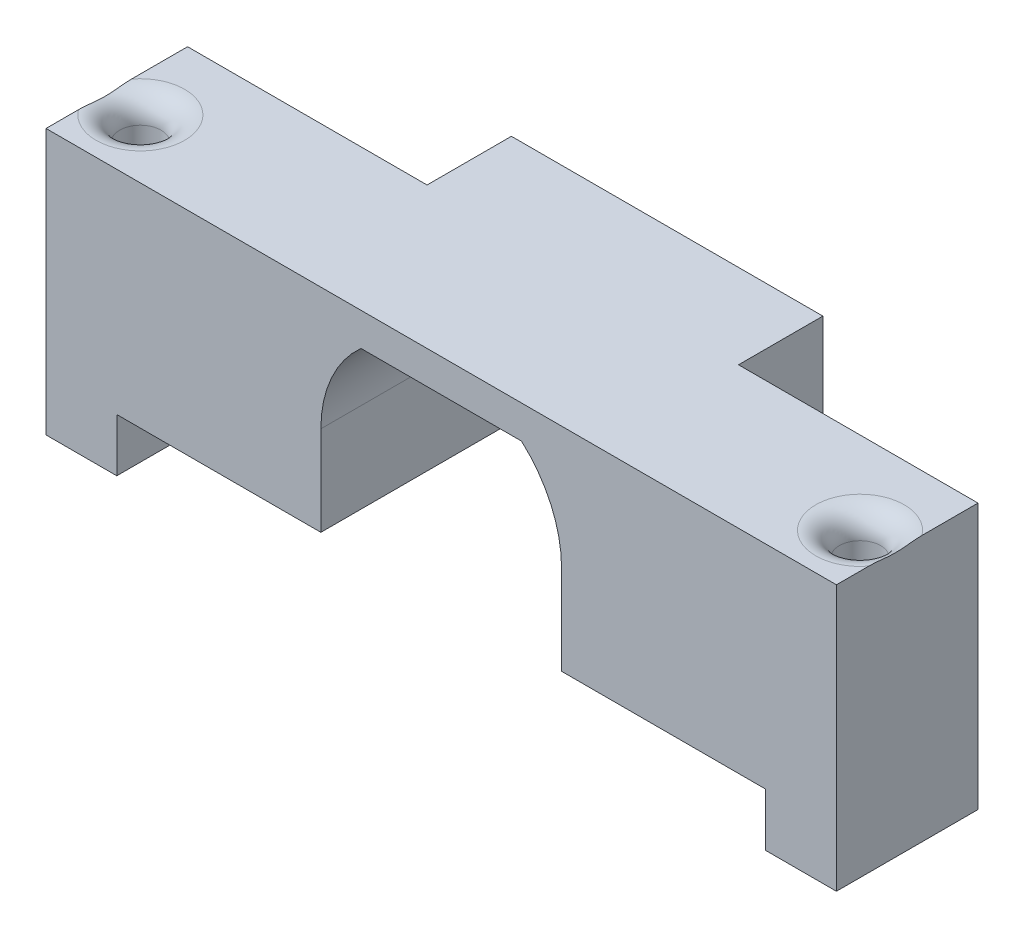
SolidWorks part; units mm, degrees
ref_plane "Front Plane" through (0, 0, 0) normal (0, 0, 1) x (1, 0, 0)
ref_plane "Top Plane" through (0, 0, 0) normal (0, 1, 0) x (1, 0, 0)
ref_plane "Right Plane" through (0, 0, 0) normal (1, 0, 0) x (0, 0, -1)
sketch "Sketch1" plane through (0, 0, 0) normal (0, 0, 1) x (1, 0, 0)
  line L0 (27.5, 0) -> (27.5, 18) construction
  line L1 (0, 0) -> (17.3, 0)
  line L2 (0, 0) -> (0, 18)
  line L3 (0, 18) -> (55, 18)
  line L4 (55, 0) -> (55, 18)
  line L5 (20.6971, 15.2) -> (34.3029, 15.2)
  line L7 (17.3, 0) -> (17.3, 7.6)
  line L8 (37.7, 0) -> (37.7, 7.6)
  line L9 (20.6971, 15.2) -> (34.3029, 15.2)
  line L10 (17.3, 0) -> (37.7, 15.2) construction
  line L11 (17.3, 15.2) -> (37.7, 0) construction
  line L12 (0, 15.2) -> (55, 15.2) construction
  line L13 (37.7, 0) -> (55, 0)
  line L14 (0, 0) -> (55, 0) construction
  line L15 (17.3, 7.6) -> (17.3, 15.2)
  line L16 (17.3, 15.2) -> (37.7, 15.2)
  line L17 (37.7, 15.2) -> (37.7, 7.6)
  arc A2 (20.6971, 15.2) -> (17.3, 7.6) centre (27.5, 7.6) ccw
  arc A3 (37.7, 7.6) -> (34.3029, 15.2) centre (27.5, 7.6) ccw
  dimension "D3" = 10.2
  dimension "D6" = 20.4
  dimension "D1" = 55
  dimension "D2" = 18
  dimension "D5" = 10.2
  dimension "D4" = 15.2
extrude "Boss-Extrude2" add sketch "Sketch1" along normal blind 12 contours L16 L17 L8 L13 L4 L3 L2 L1 L7 L15 L5 | A2 L16 L15 | A3 L17 L16 region at (0.5787, 9, 0) region at (18.2816, 13.3691, 0) region at (36.7184, 13.3691, 0)
sketch "Sketch2" plane through (0, 0, 0) normal (-1, 0, 0) x (0, 0, 1)
  line L0 (12, 0) -> (12, 18) construction
  line L5 (12, 0) -> (0, 0) construction
  line L6 (0, 18) -> (12, 18)
  line L7 (0, 18) -> (0, -4.5)
  line L8 (0, -4.5) -> (12, -4.5)
  line L9 (12, 18) -> (12, -4.5)
  dimension "D1" = 4.5
extrude "Boss-Extrude3" add sketch "Sketch2" along normal blind 6
sketch "Sketch3" plane through (55, 0, 0) normal (1, 0, 0) x (0, 0, -1)
  line L1 (-12, 18) -> (0, 18)
  line L2 (-12, 18) -> (-12, -4.5)
  line L3 (-12, -4.5) -> (0, -4.5)
  line L4 (0, 18) -> (0, -4.5)
extrude "Boss-Extrude4" add sketch "Sketch3" along normal blind 6
sketch "Sketch4" plane through (0, 18, 0) normal (0, 1, 0) x (1, 0, 0)
  line L0 (0, 0) -> (0, -12) construction
  line L1 (-6, -12) -> (-6, 0) construction
  line L3 (27.5, 0) -> (27.5, -12) construction
  line L4 (-6, 0) -> (61, 0) construction
  line L5 (-6, -12) -> (61, -12) construction
  line L6 (0, 0) -> (0, -12) construction
  circle A0 centre (-3, -7) radius 1.75
  circle A1 centre (58, -7) radius 1.75
  dimension "D1" = 3.5
  dimension "D2" = 3
  dimension "D3" = 5
extrude "Cut-Extrude1" cut sketch "Sketch4" against normal up to surface (22.5 mm away) up to face at (-3, -4.5, 6)
fillet "Fillet1" radius 2 2 edges at (58, 18, 5.25) (-3, 18, 8.75)
sketch "Sketch5" plane through (0, 0, 0) normal (0, 0, -1) x (-1, 0, 0)
  line L0 (-37.7, 7.6) -> (-17.3, 7.6) construction
  line L1 (-37.7, 0) -> (-40.7, 0)
  line L2 (-37.7, 0) -> (-55, 0) construction
  line L3 (-40.7, 0) -> (-40.7, 18)
  line L4 (6, 18) -> (-61, 18) construction
  line L5 (-40.7, 18) -> (-14.3, 18)
  line L6 (-27.5, 18) -> (-27.5, 0) construction
  line L7 (-17.3, 6) -> (-17.3, 0)
  line L8 (-20.6971, 15.2) -> (-34.3029, 15.2) construction
  line L9 (-37.7, 7.6) -> (-37.7, 0) construction
  line L10 (-20.6971, 15.2) -> (-34.3029, 15.2)
  line L11 (-37.7, 6) -> (-37.7, 0)
  line L12 (-14.3, 0) -> (-14.3, 18)
  line L13 (-17.3, 0) -> (-14.3, 0)
  arc A0 (-37.7, 6) -> (-37.5745, 9.1951) centre (-37.7, 7.6) ccw
  arc A1 (-34.3029, 15.2) -> (-37.7, 7.6) centre (-27.5, 7.6) ccw construction
  arc A2 (-34.3029, 15.2) -> (-37.5745, 9.1951) centre (-27.5, 7.6) ccw
  arc A3 (-20.6971, 15.2) -> (-17.4255, 9.1951) centre (-27.5, 7.6) cw
  arc A4 (-17.3, 6) -> (-17.4255, 9.1951) centre (-17.3, 7.6) cw
  point P22 (-27.5, 15.2)
  dimension "D1" = 3.2
  dimension "D2" = 3
extrude "Boss-Extrude5" add sketch "Sketch5" along normal blind 4.65
sketch "Sketch6" plane through (0, 0, -4.65) normal (0, 0, -1) x (-1, 0, 0)
  line L0 (-27.5, 18) -> (-27.5, 0) construction
  line L1 (-14.3, 18) -> (-40.7, 18) construction
  line L2 (-36.1012, 7.5372) -> (-18.8988, 7.5372) construction
  line L3 (-40.7, 18) -> (-40.7, 0)
  line L4 (-40.7, 0) -> (-37.7, 0) construction
  line L5 (-40.7, 18) -> (-40.7, 0) construction
  line L6 (-40.7, 0) -> (-14.3, 0)
  line L7 (-17.3, 0) -> (-14.3, 0) construction
  line L8 (-14.3, 0) -> (-14.3, 18)
  line L9 (-14.3, 18) -> (-40.7, 18)
  arc A0 (-37.7, 6) -> (-37.5745, 9.1951) centre (-37.7, 7.6) ccw construction
  arc A1 (-17.4255, 9.1951) -> (-17.3, 6) centre (-17.3, 7.6) ccw construction
  circle A2 centre (-27.5, 7.5372) radius 4.925
  dimension "D1" = 9.85
extrude "Boss-Extrude6" add sketch "Sketch6" along normal blind 2.5
